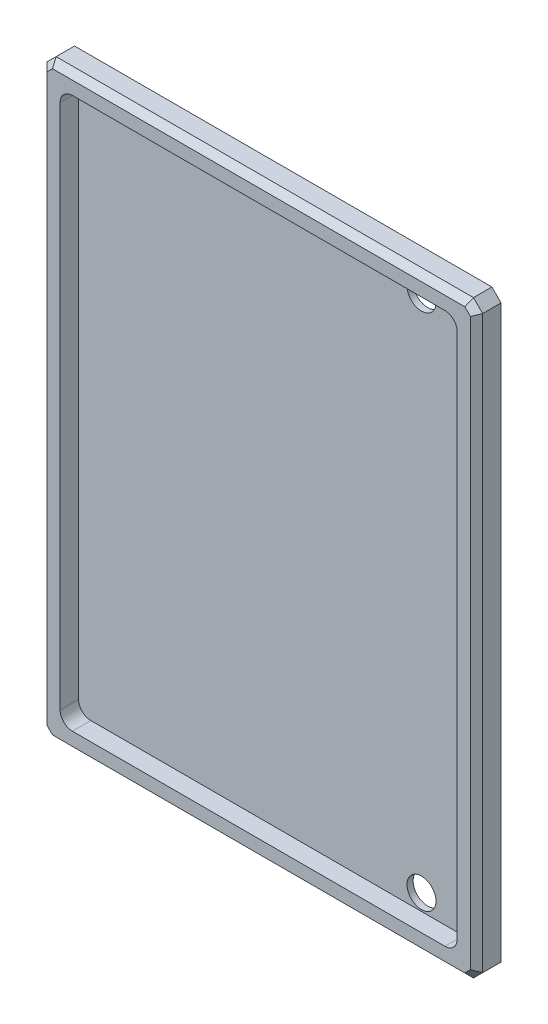
SolidWorks part; units mm, degrees
material "AISI 304"
ref_plane "Front Plane" through (0, 0, 0) normal (0, 0, 1) x (1, 0, 0)
ref_plane "Top Plane" through (0, 0, 0) normal (0, 1, 0) x (1, 0, 0)
ref_plane "Right Plane" through (0, 0, 0) normal (1, 0, 0) x (0, 0, -1)
sketch "Sketch1" plane through (0, 0, 0) normal (0, 0, 1) x (1, 0, 0)
  line L1 (112.7125, -152.4) -> (-112.7125, -152.4)
  line L2 (112.7125, -152.4) -> (112.7125, 152.4)
  line L3 (112.7125, 152.4) -> (-112.7125, 152.4)
  line L4 (-112.7125, -152.4) -> (-112.7125, 152.4)
  line L5 (112.7125, -152.4) -> (-112.7125, 152.4) construction
  line L6 (112.7125, 152.4) -> (-112.7125, -152.4) construction
  point P0 (0, 0)
  dimension "D1" = 304.8
  dimension "D2" = 225.425
extrude "Boss-Extrude1" add sketch "Sketch1" along normal blind 12.7
sketch "Sketch2" plane through (0, 0, 12.7) normal (0, 0, 1) x (1, 0, 0)
  line L0 (-112.7125, 152.4) -> (-112.7125, -152.4) construction
  line L1 (96.3625, -142.4) -> (-96.3625, -142.4)
  line L2 (102.7125, -136.05) -> (102.7125, 136.05)
  line L3 (96.3625, 142.4) -> (-96.3625, 142.4)
  line L4 (-102.7125, -136.05) -> (-102.7125, 136.05)
  line L5 (102.7125, -142.4) -> (-102.7125, 142.4) construction
  line L6 (102.7125, 142.4) -> (-102.7125, -142.4) construction
  line L7 (112.7125, 152.4) -> (-112.7125, 152.4) construction
  arc A0 (-96.3625, -142.4) -> (-102.7125, -136.05) centre (-96.3625, -136.05) cw
  arc A1 (96.3625, -142.4) -> (102.7125, -136.05) centre (96.3625, -136.05) ccw
  arc A2 (102.7125, 136.05) -> (96.3625, 142.4) centre (96.3625, 136.05) ccw
  arc A3 (-96.3625, 142.4) -> (-102.7125, 136.05) centre (-96.3625, 136.05) ccw
  point P0 (0, 0)
  dimension "D3" = 6.35
  dimension "D1" = 10
  dimension "D2" = 10
extrude "Cut-Extrude1" cut sketch "Sketch2" against normal blind 9.525
sketch "Sketch4" plane through (0, 0, 0) normal (0, 0, -1) x (-1, 0, 0)
  line L1 (-112.7125, -152.4) -> (-112.7125, 152.4) construction
  line L2 (0, 0) -> (-117.2439, 0) construction
  line L3 (96.3625, -142.4) -> (-96.3625, -142.4) construction
  circle A0 centre (-74.7125, -134.05) radius 7.5
  circle A1 centre (-74.7125, 134.05) radius 7.5
  dimension "D1" = 15
  dimension "D2" = 8.35
  dimension "D3" = 38
  dimension "D4" = 0
extrude "Cut-Extrude3" cut sketch "Sketch4" against normal through all
hole_wizard "M4x0.7 Tapped Hole1" positions "Sketch10" profile "Sketch11" tap size "M4x0.7" standard "ANSI Metric"
sketch "Sketch10" plane through (0, 0, 0) normal (0, 0, -1) x (-1, 0, 0)
  line L0 (112.7125, 152.4) -> (112.7125, -152.4) construction
  line L1 (-112.7125, 152.4) -> (112.7125, 152.4) construction
  point P0 (107.7125, -113.6)
  point P2 (107.7125, 113.6)
  dimension "D1" = 5
  dimension "D2" = 38.8
  dimension "D3" = 266
sketch "Sketch11" plane through (-107.7125, -113.6, 0) normal (1, 0, 0) x (0, 1, 0)
  line L0 (0, 0) -> (0, 6.3914)
  line L1 (0, 6.3914) -> (1.65, 5.4)
  line L2 (1.65, 5.4) -> (1.65, 0)
  line L5 (1.65, 0) -> (0, 0)
  line L10 (0, 6.3914) -> (-1.65, 5.4) construction
  line L11 (0, -6.35) -> (0, 107.95) construction
  dimension "Tap Drill Dia." = 3.3
  dimension "Tap Drill Depth" = 5.4
  dimension "Drill Angle" = 118
cosmetic thread "Hole Thread1" parameters "D1"=3, "D2"=4.3
cosmetic thread "Hole Thread2" parameters "D1"=3, "D2"=4.3
chamfer "Chamfer1" distance 4.7625 angle 45 4 edges at (-112.7125, 152.4, 6.35) (112.7125, 152.4, 6.35) (112.7125, -152.4, 6.35) (-112.7125, -152.4, 6.35)
chamfer "Chamfer2" distance 3.175 angle 45 8 edges at (110.3313, -150.0188, 12.7) (112.7125, 0, 12.7) (110.3313, 150.0187, 12.7) (0, 152.4, 12.7) (-110.3312, 150.0187, 12.7) (-112.7125, 0, 12.7) (-110.3313, -150.0188, 12.7) (0, -152.4, 12.7)
